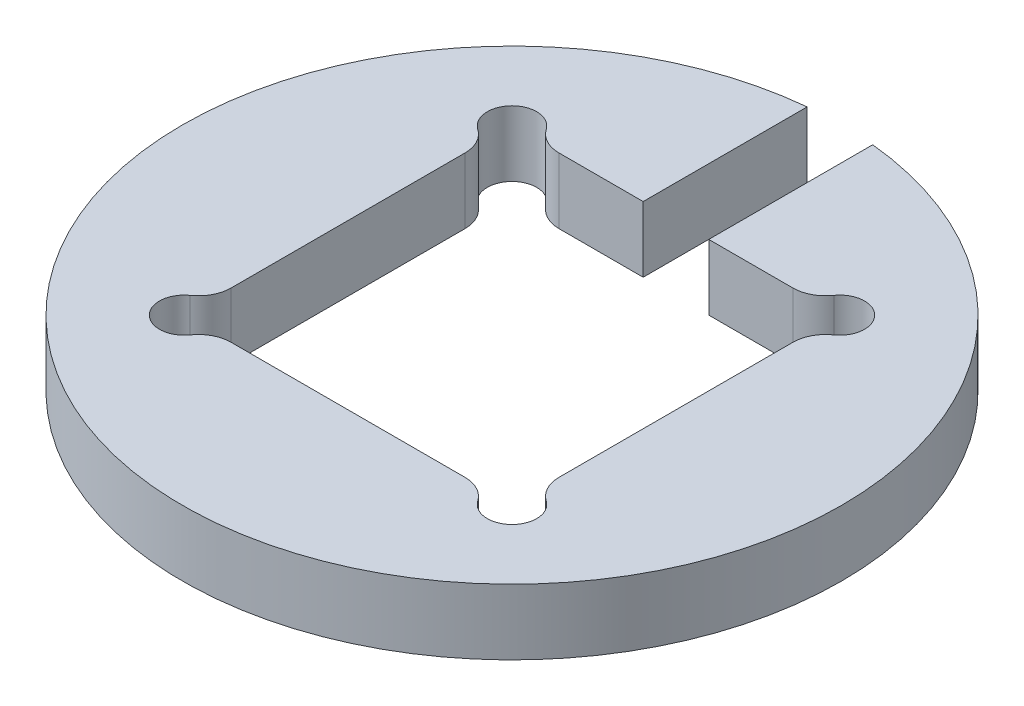
SolidWorks part; units mm, degrees
ref_plane "Front Plane" through (0, 0, 0) normal (0, 0, 1) x (1, 0, 0)
ref_plane "Top Plane" through (0, 0, 0) normal (0, 1, 0) x (1, 0, 0)
ref_plane "Right Plane" through (0, 0, 0) normal (1, 0, 0) x (0, 0, -1)
sketch "Sketch1" plane through (0, 0, 0) normal (0, 1, 0) x (1, 0, 0)
  line L0 (0, 0) -> (0, 20)
  line L1 (0, 20) -> (8, 20)
  line L2 (8, 20) -> (8, 30)
  line L3 (0, 0) -> (20, 0)
  line L4 (20, 0) -> (20, 20)
  line L5 (20, 20) -> (12, 20)
  line L6 (12, 20) -> (12, 30)
  line L7 (0, 10) -> (20, 10) construction
  arc A2 (12, 30) -> (8, 30) centre (10, 10) cw
  arc A3 (18.5, 20) -> (20, 18.5) centre (20, 20) cw
  arc A4 (20, 1.5) -> (18.5, 0) centre (20, 0) cw
  arc A5 (1.5, 0) -> (0, 1.5) centre (0, 0) cw
  arc A6 (1.5, 20) -> (0, 18.5) centre (0, 20) ccw
  point P20 (0, 0)
  dimension "D1" = 20
  dimension "D7" = 1.5
  dimension "D5" = 1.5
  dimension "D8" = 1.5
  dimension "D9" = 1.5
  dimension "D2" = 20
  dimension "D3" = 4
  dimension "D4" = 10
extrude "Boss-Extrude1" add sketch "Sketch1" along normal blind 4 contours A6 L1 L2 A2 L6 L5 A3 L4 A4 L3 A5 L0 region at (-1.4622, 0, 1.4622)
fillet "Fillet1" radius 2 8 edges at (18.5, 2, 0) (20, 2, -1.5) (20, 2, -18.5) (0, 2, -1.5) (1.5, 2, 0) (0, 2, -18.5) (18.5, 2, -20) (1.5, 2, -20)
